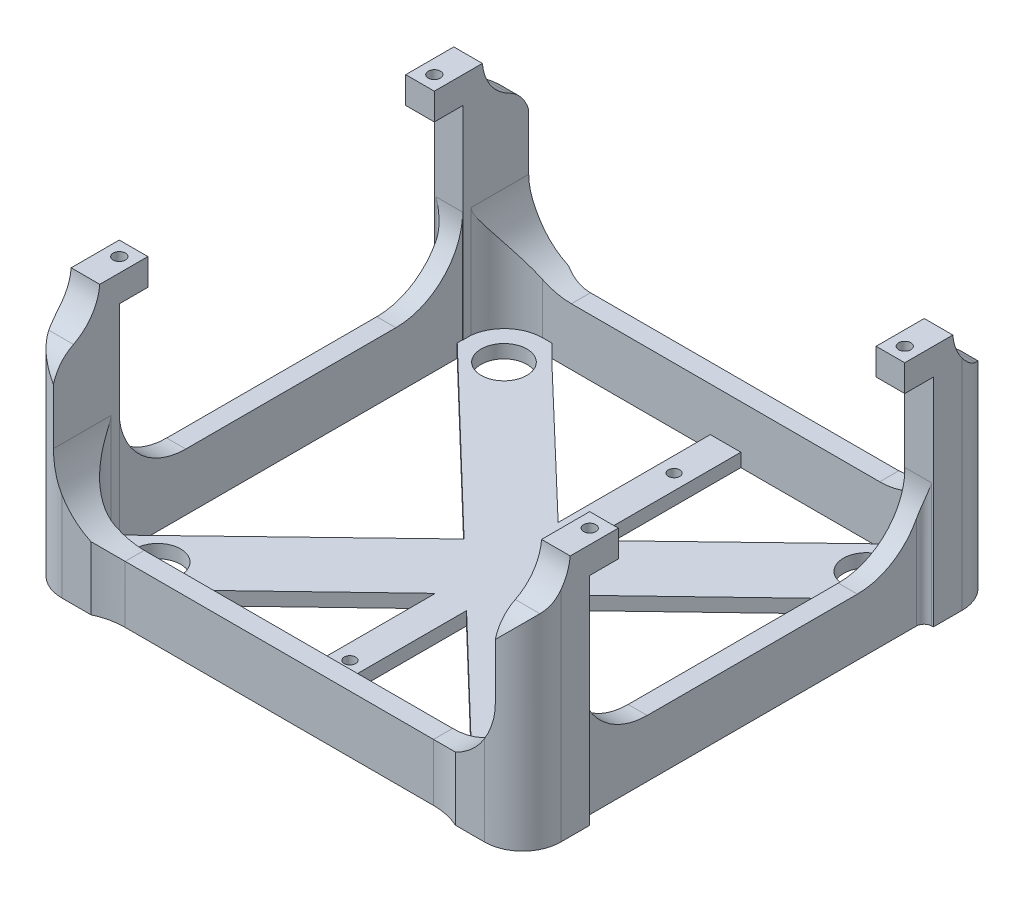
SolidWorks part; units mm, degrees
material "ABS"
ref_plane "Front Plane" through (0, 0, 0) normal (0, 0, 1) x (1, 0, 0)
ref_plane "Top Plane" through (0, 0, 0) normal (0, 1, 0) x (1, 0, 0)
ref_plane "Right Plane" through (0, 0, 0) normal (1, 0, 0) x (0, 0, -1)
sketch "Sketch1" plane through (0, 0, 0) normal (0, 1, 0) x (1, 0, 0)
  line L0 (-58, -56) -> (58, -56)
  line L1 (-58, -56) -> (-58, 56)
  line L2 (58, -56) -> (58, 56)
  line L3 (-58, 56) -> (58, 56)
  line L4 (-58, -56) -> (58, 56) construction
  line L5 (58, -56) -> (-58, 56) construction
  line L6 (-63, -61) -> (-63, 61)
  line L7 (-63, 61) -> (63, 61)
  line L8 (63, -61) -> (63, 61)
  line L9 (-63, -61) -> (63, -61)
  point P1 (0, 0)
  dimension "D1" = 116
  dimension "D2" = 112
  dimension "D3" = 5
extrude "Boss-Extrude1" add sketch "Sketch1" along normal blind 15
fillet "Fillet1" radius 10 1 edges at (58, 7.5, -56)
fillet "Fillet2" radius 10 1 edges at (-58, 7.5, -56)
fillet "Fillet3" radius 10 1 edges at (-58, 7.5, 56)
fillet "Fillet4" radius 10 1 edges at (58, 7.5, 56)
sketch "Sketch4" plane through (0, 15, 0) normal (0, 1, 0) x (1, 0, 0)
  line L0 (-63, 61) -> (-63, 62.625)
  line L1 (-63, 62.625) -> (-61.675, 62.625)
  line L2 (-61.675, 62.625) -> (-61.675, 80.1975)
  line L3 (-61.675, 80.1975) -> (-57.925, 80.1975)
  line L4 (-65.425, 45.0525) -> (-65.425, 80.1975)
  line L5 (-65.425, 45.0525) -> (-57.925, 45.0525)
  line L6 (-65.425, 80.1975) -> (-57.925, 80.1975)
  line L7 (-57.925, 45.0525) -> (-57.925, 80.1975)
  line L8 (-65.425, 45.0525) -> (-57.925, 80.1975) construction
  line L9 (-65.425, 80.1975) -> (-57.925, 45.0525) construction
  dimension "D1" = 1.625
  dimension "D2" = 1.325
  dimension "D3" = 3.75
extrude "Boss-Extrude3" add sketch "Sketch4" along normal blind 49.75 and the other way up to surface contours L6 L4 L5 L7
sketch "Sketch5" plane through (-57.925, 0, 0) normal (1, 0, 0) x (0, 0, -1)
  line L0 (45.0525, 64.75) -> (80.1975, 64.75) construction
  circle A0 centre (62.625, 64.75) radius 12.5
  dimension "D1" = 25
extrude "Cut-Extrude1" cut sketch "Sketch5" against normal through all
ref_plane "Plane1" through (-61.675, 0, 0) normal (1, 0, 0) x (0, 0, -1)
sketch "Sketch6" plane through (-57.925, 0, 0) normal (1, 0, 0) x (0, 0, -1)
  line L0 (45.0525, 64.75) -> (50.125, 64.75)
  line L1 (45.0525, 64.75) -> (45.0525, 57.25)
  line L2 (45.0525, 0) -> (45.0525, 64.75) construction
  line L3 (45.0525, 57.25) -> (52.625, 57.25)
  arc A0 (50.125, 64.75) -> (75.125, 64.75) centre (62.625, 64.75) ccw construction
  arc A1 (52.625, 57.25) -> (50.125, 64.75) centre (62.625, 64.75) cw
  dimension "D1" = 7.5
extrude "Boss-Extrude4" add sketch "Sketch6" along normal blind 5
sketch "Sketch9" plane through (0, 64.75, 0) normal (0, 1, 0) x (1, 0, 0)
  line L0 (-52.925, 47.5887) -> (-55.425, 47.5887)
  line L1 (-52.925, 50.125) -> (-52.925, 45.0525) construction
  circle A0 centre (-55.425, 47.5887) radius 1.25
  dimension "D2" = 2.5
  dimension "D1" = 2.5
extrude "Cut-Extrude3" cut sketch "Sketch9" against normal through all
mirror "Mirror1" about plane through (-61.675, 0, 0) normal (1, 0, 0) of "Cut-Extrude3", "Boss-Extrude4"
ref_plane "Plane2" through (0, 0, -62.625) normal (0, 0, -1) x (-1, 0, 0)
mirror "Mirror2" about plane through (0, 0, -62.625) normal (0, 0, -1) of "Mirror1", "Boss-Extrude4", "Cut-Extrude3"
fillet "Fillet6" radius 17.5 1 edges at (-57.925, 7.5, -61)
fillet "Fillet7" radius 17.5 3 edges at (-52.7994, 15, -66.1256) (-54.6248, 15, -53.4908) (-57.925, 15, -62.8612)
fillet "Fillet8" radius 2 1 edges at (-63, 7.5, -45.0525)
fillet "Fillet9" radius 17.5 2 edges at (-63.5858, 15, -44.4667) (-61.5, 15, -45.0525)
fillet "Fillet10" radius 17.5 2 edges at (-57.925, 0, -79.3488) (-61.675, 0, -80.1975)
mirror "Mirror4" about plane through (0, 0, 0) normal (0, 0, 1) of "Mirror2", "Mirror1", "Cut-Extrude3", "Boss-Extrude4", "Cut-Extrude1", "Boss-Extrude3"
fillet "Fillet11" radius 2 1 edges at (-63, 7.5, 45.0525)
fillet "Fillet12" radius 17.5 2 edges at (-61.5, 15, 45.0525) (-63.5858, 15, 44.4667)
fillet "Fillet13" radius 17.5 1 edges at (-57.925, 7.5, 61)
fillet "Fillet14" radius 17.5 3 edges at (-54.6248, 15, 53.4908) (-57.925, 15, 62.8612) (-52.7994, 15, 66.1256)
fillet "Fillet15" radius 17.5 2 edges at (-57.925, 0, 79.3488) (-61.675, 0, 80.1975)
mirror "Mirror6" about plane through (0, 0, 0) normal (1, 0, 0) of "Mirror4", "Boss-Extrude3", "Boss-Extrude4", "Cut-Extrude3", "Mirror1", "Mirror2"
fillet "Fillet16" radius 2 1 edges at (63, 7.5, 45.0525)
fillet "Fillet17" radius 17.5 2 edges at (61.5, 15, 45.0525) (63.5858, 15, 44.4667)
fillet "Fillet18" radius 2 1 edges at (63, 7.5, -45.0525)
fillet "Fillet19" radius 17.5 2 edges at (61.5, 15, -45.0525) (63.5858, 15, -44.4667)
fillet "Fillet20" radius 17.5 1 edges at (57.925, 7.5, -61)
fillet "Fillet21" radius 17.5 3 edges at (54.6248, 15, -53.4908) (57.925, 15, -62.8612) (52.7994, 15, -66.1256)
fillet "Fillet22" radius 17.5 1 edges at (57.925, 7.5, 61)
fillet "Fillet23" radius 17.5 3 edges at (57.925, 15, 62.8612) (54.6248, 15, 53.4908) (52.7994, 15, 66.1256)
fillet "Fillet24" radius 17.5 2 edges at (57.925, 0, 79.3488) (61.675, 0, 80.1975)
fillet "Fillet25" radius 17.5 2 edges at (57.925, 0, -79.3488) (61.675, 0, -80.1975)
sketch "Sketch11" plane through (0, 0, 0) normal (0, -1, 0) x (-1, 0, 0)
  line L0 (0, 0) -> (0, 45.4)
  line L1 (0, 45.4) -> (-47.5, 45.4)
  line L3 (-55, 0) -> (55, 0) construction
  line L4 (0, 55) -> (0, -55) construction
  line L5 (-47.5, 45.4) -> (47.5, -45.4)
  line L6 (47.5, -45.4) -> (41.3679, -51.8158)
  line L7 (41.3679, -51.8158) -> (-58, 43.159)
  line L8 (-58, -45.0525) -> (-58, 45.0525) construction
  line L9 (41.3679, -51.8158) -> (45.5521, -56)
  line L10 (48, -56) -> (-48, -56) construction
  line L11 (47.5, -45.4) -> (55.1513, -40.903)
  line L12 (-47.5, 45.4) -> (-41.2244, 51.6756)
  line L13 (-41.2244, 51.6756) -> (55.1513, -40.903)
  line L14 (55.1513, -40.903) -> (58, -43.6395)
  line L15 (58, 45.0525) -> (58, -45.0525) construction
  line L16 (-41.2244, 51.6756) -> (-45.7262, 56)
  line L17 (-48, 56) -> (48, 56) construction
  circle A0 centre (-47.5, 45.4) radius 6
  circle A1 centre (-47.5, 45.4) radius 8.875
  circle A4 centre (-47.5, -45.4) radius 8.875
  circle A5 centre (-47.5, -45.4) radius 6
  circle A6 centre (47.5, 45.4) radius 8.875
  circle A7 centre (47.5, 45.4) radius 6
  circle A8 centre (47.5, -45.4) radius 8.875
  circle A9 centre (47.5, -45.4) radius 6
  arc A10 (-58, 43.159) -> (-45.7262, 56) centre (-47.5655, 45.4717) cw
  arc A11 (45.5521, -56) -> (58, -43.6395) centre (48.2746, -46.2936) ccw
  line M27 (-58, -45.0525) -> (-58, 45.0525)
  line M28 (-58, 45.0525) -> (-57.925, 45.0525)
  line M29 (-57.925, 45.0525) -> (-57.925, 47.2224)
  arc M30 (-57.925, 47.2224) -> (-48, 56) centre (-48, 46) cw
  line M31 (-48, 56) -> (48, 56)
  line M35 (58, 45.0525) -> (58, -45.0525)
  line M36 (58, -45.0525) -> (57.925, -45.0525)
  line M37 (57.925, -45.0525) -> (57.925, -47.2224)
  arc M38 (57.925, -47.2224) -> (48, -56) centre (48, -46) cw
  line M39 (48, -56) -> (-48, -56)
  dimension "D3" = 12
  dimension "D4" = 17.75
  dimension "D1" = 45.4
  dimension "D2" = 47.5
extrude "Boss-Extrude5" add sketch "Sketch11" against normal blind 3.5 contours A8 L9 L14 M39 M38 M37 M36 M35 | A9 L6 A8 L11 | A9 L5 A8 L6 | A9 L11 L13 A8 L5 | A8 L5 A1 L7 | A8 L13 L0 L5 | A1 L5 L0 L13 L1 | A1 L1 L13 | L5 A1 L1 A0 | L1 A1 L12 A0 | A1 L5 A0 L12 L16 | A1 L16 L7 M31 M30 M29 M28 M27
mirror "Mirror7" about plane through (0, 0, 0) normal (0, 0, 1) of "Boss-Extrude5"
sketch "Sketch12" plane through (0, 0, 0) normal (0, -1, 0) x (-1, 0, 0)
  line L0 (0, 0) -> (-4, 0)
  line L1 (0, 0) -> (-0.0871, 56)
  line L2 (-45.7262, 56) -> (45.5521, 56) construction
  line L3 (4, -56.5079) -> (-4, -56.5079)
  line L4 (4, -56.5079) -> (4, 56.5079)
  line L5 (-4, -56.5079) -> (-4, 56.5079)
  line L6 (4, 56.5079) -> (-4, 56.5079)
  line L7 (4, -56.5079) -> (-4, 56.5079) construction
  line L8 (-4, -56.5079) -> (4, 56.5079) construction
  line M6 (-45.7262, -56) -> (-0.1051, -12.1764)
  line M7 (-0.1051, -12.1764) -> (41.3679, -51.8158)
  line M9 (45.5521, -56) -> (-45.7262, -56)
  line M13 (41.3679, 51.8158) -> (-0.1051, 12.1764)
  line M14 (-0.1051, 12.1764) -> (-45.7262, 56)
  line M15 (-45.7262, 56) -> (45.5521, 56)
  dimension "D1" = 4
extrude "Boss-Extrude6" add sketch "Sketch12" against normal up to surface (3.5 mm away) contours L4 L1 M13 M15 M14 | L5 L1 M14 M15 | L5 L4 M9 M7 M6 up to face at (47.5, 3.5, -51.4)
sketch "Sketch13" plane through (0, 0, 0) normal (0, -1, 0) x (-1, 0, 0)
  line L0 (0, 0) -> (0, 42.5)
  circle A0 centre (0, 42.5) radius 1.5
  dimension "D2" = 3
  dimension "D1" = 42.5
extrude "Cut-Extrude4" cut sketch "Sketch13" against normal through all
mirror "Mirror8" about plane through (0, 0, 0) normal (0, 0, 1) of "Cut-Extrude4"
sketch "Sketch14" plane through (0, 57.25, 0) normal (0, -1, 0) x (-1, 0, 0)
  line L1 (65.425, -72.625) -> (70.425, -72.625)
  line L2 (65.425, -72.625) -> (65.425, -80.1975)
  line L3 (65.425, -80.1975) -> (70.425, -80.1975)
  line L4 (70.425, -72.625) -> (70.425, -80.1975)
  line L5 (52.925, -72.625) -> (57.925, -72.625)
  line L6 (52.925, -72.625) -> (52.925, -80.1975)
  line L7 (52.925, -80.1975) -> (57.925, -80.1975)
  line L8 (57.925, -72.625) -> (57.925, -80.1975)
  line L9 (65.425, -52.625) -> (70.425, -52.625)
  line L10 (65.425, -52.625) -> (65.425, -45.0525)
  line L11 (65.425, -45.0525) -> (70.425, -45.0525)
  line L12 (70.425, -52.625) -> (70.425, -45.0525)
  line L13 (57.925, -52.625) -> (52.925, -52.625)
  line L14 (57.925, -52.625) -> (57.925, -45.0525)
  line L15 (57.925, -45.0525) -> (52.925, -45.0525)
  line L16 (52.925, -52.625) -> (52.925, -45.0525)
extrude "Cut-Extrude5" cut sketch "Sketch14" against normal through all
mirror "Mirror9" about plane through (0, 0, 0) normal (0, 0, 1) of "Cut-Extrude5"
mirror "Mirror10" about plane through (0, 0, 0) normal (1, 0, 0) of "Mirror9", "Cut-Extrude5"
sketch "Sketch15" plane through (0, 64.75, 0) normal (0, 1, 0) x (1, 0, 0)
  line L0 (-65.425, -80.1975) -> (-65.425, -87.6975)
  line L2 (-65.425, -87.6975) -> (-57.925, -87.6975)
  line L3 (-65.425, -87.6975) -> (-65.425, -80.1975)
  line L4 (-65.425, -80.1975) -> (-57.925, -80.1975)
  line L5 (-57.925, -87.6975) -> (-57.925, -80.1975)
  line M2 (-65.425, -80.1975) -> (-57.925, -80.1975)
  dimension "D1" = 7.5
extrude "Boss-Extrude7" add sketch "Sketch15" against normal blind 6 contours L2 L5 L0 M2
sketch "Sketch16" plane through (0, 58.75, 0) normal (0, -1, 0) x (-1, 0, 0)
  line L0 (57.925, -83.9475) -> (65.425, -83.9475)
  line L1 (57.925, -87.6975) -> (57.925, -80.1975) construction
  line L2 (65.425, -80.1975) -> (65.425, -87.6975) construction
  circle A0 centre (61.675, -83.9475) radius 1.6
  dimension "D1" = 3.2
extrude "Cut-Extrude6" cut sketch "Sketch16" against normal through all contours A0
ref_plane "Plane3" through (0, 0, 62.625) normal (0, 0, 1) x (1, 0, 0)
mirror "Mirror11" about plane through (0, 0, 62.625) normal (0, 0, 1) of "Cut-Extrude6", "Boss-Extrude7"
mirror "Mirror12" about plane through (0, 0, 0) normal (0, 0, 1) of "Mirror11", "Cut-Extrude6", "Boss-Extrude7"
mirror "Mirror13" about plane through (0, 0, 0) normal (1, 0, 0) of "Mirror12", "Mirror11", "Cut-Extrude6", "Boss-Extrude7"
ref_plane "Plane4" through (0, 42.25, 0) normal (0, 1, 0) x (1, 0, 0)
sketch "Sketch17" plane through (0, 0, 62.625) normal (0, 0, 1) x (1, 0, 0)
  circle A0 centre (0, 0) radius 340.0444
extrude "Cut-Extrude7" cut sketch "Sketch17" along normal through all
ref_plane "Plane5" through (0, 0, 0) normal (0, 0, -1) x (-1, 0, 0)
mirror "Mirror14" about plane through (0, 0, 0) normal (0, 0, -1) of "Cut-Extrude7"
fillet "Fillet26" radius 10 1 edges at (61.675, 52.25, -62.625)
fillet "Fillet27" radius 10 1 edges at (-61.675, 52.25, -62.625)
fillet "Fillet28" radius 10 1 edges at (61.675, 52.25, 62.625)
fillet "Fillet29" radius 10 1 edges at (-61.675, 52.25, 62.625)
sketch "Sketch18" plane through (0, 58.75, 0) normal (0, -1, 0) x (-1, 0, 0)
  line L1 (-57.925, 45.0525) -> (-65.425, 45.0525)
  line L2 (-57.925, 45.0525) -> (-57.925, 37.5525)
  line L3 (-57.925, 37.5525) -> (-65.425, 37.5525)
  line L4 (-65.425, 45.0525) -> (-65.425, 37.5525)
  circle A0 centre (-61.675, 41.3025) radius 1.6
  dimension "D1" = 3.2
extrude "Boss-Extrude8" add sketch "Sketch18" along normal blind 2
mirror "Mirror15" about plane through (0, 0, 0) normal (0, 0, -1) of "Boss-Extrude8"
mirror "Mirror16" about plane through (0, 0, 0) normal (1, 0, 0) of "Mirror15", "Boss-Extrude8"
sketch "Sketch19" plane through (0, 64.75, 0) normal (0, 1, 0) x (1, 0, 0)
  circle A0 centre (0, 0) radius 163.759
extrude "Cut-Extrude8" cut sketch "Sketch19" against normal blind 1
fillet "Fillet30" radius 10 4 edges at (-65.425, 22.2972, -62.625) (-57.925, 38.5472, -62.625) (-61.675, 44.5944, -62.625) (-65.425, 49.8648, -61.1234)
fillet "Fillet31" radius 10 4 edges at (-65.425, 22.2972, 62.625) (-57.925, 38.5472, 62.625) (-61.675, 44.5944, 62.625) (-65.425, 49.8648, 61.1234)
fillet "Fillet32" radius 10 4 edges at (57.925, 38.5472, 62.625) (65.425, 22.2972, 62.625) (61.675, 44.5944, 62.625) (65.425, 49.8648, 61.1234)
fillet "Fillet33" radius 10 4 edges at (57.925, 38.5472, -62.625) (65.425, 22.2972, -62.625) (61.675, 44.5944, -62.625) (65.425, 49.8648, -61.1234)
